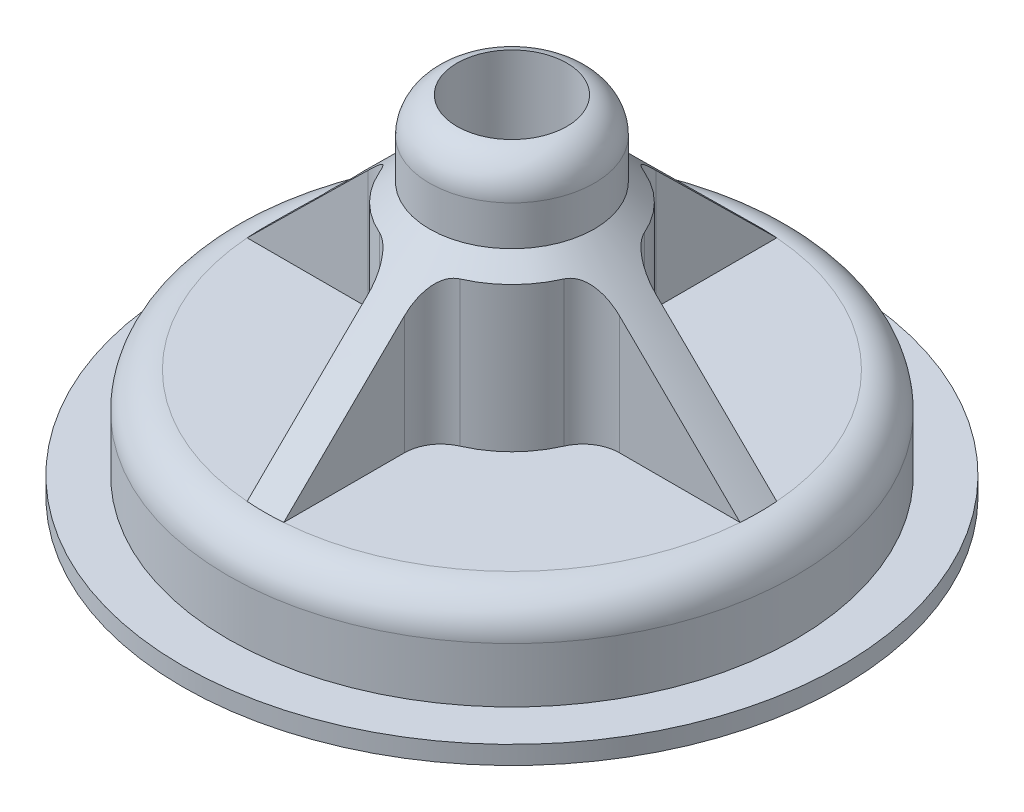
SolidWorks part; units mm, degrees
material "有机玻璃 (TM) GS 丙烯酸铸钣"
ref_plane "前视基准面" through (0, 0, 0) normal (0, 0, 1) x (1, 0, 0)
ref_plane "上视基准面" through (0, 0, 0) normal (0, 1, 0) x (1, 0, 0)
ref_plane "右视基准面" through (0, 0, 0) normal (1, 0, 0) x (0, 0, -1)
sketch "草图1" plane through (0, 0, 0) normal (0, 1, 0) x (1, 0, 0)
  circle A0 centre (0, 0) radius 18
  dimension "D1" = 36
extrude "凸台-拉伸1" add sketch "草图1" along normal blind 19
sketch "草图2" plane through (0, 0, 0) normal (0, -1, 0) x (1, 0, 0)
  circle A0 centre (0, 0) radius 14.5
  dimension "D1" = 29
extrude "切除-拉伸1" cut sketch "草图2" against normal blind 5
sketch "草图3" plane through (0, 5, 0) normal (0, -1, 0) x (1, 0, 0)
  circle A0 centre (0, 0) radius 4
  dimension "D1" = 8
extrude "切除-拉伸2" cut sketch "草图3" against normal blind 7
sketch "草图4" plane through (0, 12, 0) normal (0, -1, 0) x (1, 0, 0)
  circle A0 centre (0, 0) radius 3
  dimension "D1" = 6
extrude "切除-拉伸3" cut sketch "草图4" against normal blind 7
sketch "草图5" plane through (0, 19, 0) normal (0, 1, 0) x (1, 0, 0)
  circle A0 centre (0, 0) radius 25.1461
  circle A1 centre (0, 0) radius 15.5
  dimension "D1" = 31
extrude "切除-拉伸4" cut sketch "草图5" against normal blind 18
sketch "草图6" plane through (0, 19, 0) normal (0, 1, 0) x (1, 0, 0)
  line L2 (-1, 15.4677) -> (-1, 5.4083)
  line L4 (1, 15.4677) -> (1, 5.4083)
  line L7 (-15.4677, 1) -> (-5.4083, 1)
  line L9 (-15.4677, -1) -> (-5.4083, -1)
  line L20 (-1, -5.4083) -> (-1, -15.4677)
  line L23 (1, -5.4083) -> (1, -15.4677)
  line L24 (5.4083, -1) -> (15.4677, -1)
  line L27 (5.4083, 1) -> (15.4677, 1)
  arc A0 (-15.4677, -1) -> (-1, -15.4677) centre (0, 0) ccw
  arc A1 (-1, 5.4083) -> (-5.4083, 1) centre (0, 0) ccw
  arc A2 (-5.4083, -1) -> (-1, -5.4083) centre (0, 0) ccw
  arc A3 (1, -5.4083) -> (5.4083, -1) centre (0, 0) ccw
  arc A4 (5.4083, 1) -> (1, 5.4083) centre (0, 0) ccw
  arc A5 (-1, 15.4677) -> (-15.4677, 1) centre (0, 0) ccw
  arc A6 (15.4677, 1) -> (1, 15.4677) centre (0, 0) ccw
  arc A7 (1, -15.4677) -> (15.4677, -1) centre (0, 0) ccw
  dimension "D1" = 11
  dimension "D3" = 31
  dimension "D2" = 2
  dimension "D4" = 2
extrude "切除-拉伸5" cut sketch "草图6" against normal blind 13
sketch "草图8" plane through (0, 0, 0) normal (0, 0, 1) x (1, 0, 0)
  line L0 (-15.5, 6) -> (-22.9651, 6) construction
  line L4 (-19.272, 6) -> (-19.272, 20.8218)
  line L5 (-13.5, 6) -> (-5.4083, 14)
  line L6 (-1, 6) -> (-15.4677, 6) construction
  line L8 (-5.4083, 6) -> (-5.4083, 19) construction
  line L9 (-15.5, 19) -> (-15.5, 1) construction
  line L10 (-15.5, 6) -> (-19.272, 6)
  line L11 (-5.4083, 14) -> (-5.4083, 20.8218)
  line L12 (-5.4083, 20.8218) -> (-19.272, 20.8218)
  line L13 (-13.5, 6) -> (-15.5, 6)
  dimension "D1" = 2
  dimension "D2" = 8
revolve "切除-旋转2" cut sketch "草图8" angle 360 about axis through (0, 12, 0) along (0, -1, 0)
fillet "圆角5" radius 2 1 edges at (0, 6, 15.5)
fillet "圆角7" radius 2 8 edges at (-1, 9.9547, 5.4083) (-5.4083, 9.9547, 1) (-5.4083, 9.9547, -1) (-1, 9.9547, -5.4083) (1, 9.9547, -5.4083) (5.4083, 9.9547, -1) (5.4083, 9.9547, 1) (1, 9.9547, 5.4083)
sketch "草图9" plane through (0, 19, 0) normal (0, 1, 0) x (1, 0, 0)
  circle A0 centre (0, 0) radius 5.4083
  circle A1 centre (0, 0) radius 4.5
  dimension "D1" = 9
extrude "切除-拉伸6" cut sketch "草图9" against normal up to surface (5 mm away) up to face at (0, 14, 5.4083)
fillet "圆角8" radius 2 1 edges at (0, 19, 4.5)
